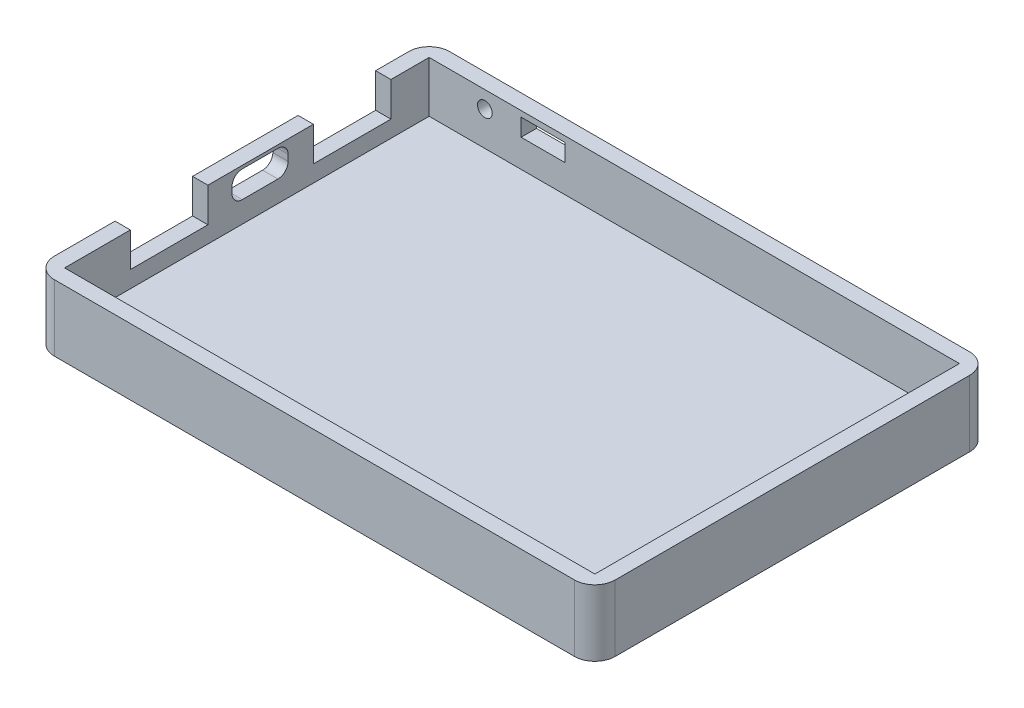
SolidWorks part; units mm, degrees
ref_plane "Front Plane" through (0, 0, 0) normal (0, 0, 1) x (1, 0, 0)
ref_plane "Top Plane" through (0, 0, 0) normal (0, 1, 0) x (1, 0, 0)
ref_plane "Right Plane" through (0, 0, 0) normal (1, 0, 0) x (0, 0, -1)
sketch "Sketch1" plane through (0, 0, 0) normal (0, 1, 0) x (1, 0, 0)
  line L1 (0, 77.5) -> (110, 77.5)
  line L2 (0, 77.5) -> (0, 0)
  line L3 (0, 0) -> (110, 0)
  line L4 (110, 77.5) -> (110, 0)
  line L6 (3, 74.5) -> (3, 3)
  line L7 (3, 3) -> (107, 3)
  line L8 (107, 74.5) -> (107, 3)
  line L9 (3, 74.5) -> (107, 74.5)
  line L10 (0, 73.5) -> (110, 73.5) construction
  line L11 (106, 77.5) -> (106, 0) construction
  point P4 (0, 0)
  dimension "D1" = 3
extrude "Boss-Extrude1" add sketch "Sketch1" along normal blind 10
extrude "Boss-Extrude2" add sketch "Sketch1<2>" against normal blind 3 contours L9 L6 L7 L8 | L4 L1 L2 L3 L6 L9 L8 L7 region at (55, 0, -76.1544) region at (55, 0, -38.75)
sketch "Sketch1<2>" plane through (0, 0, 0) normal (0, 1, 0) x (1, 0, 0) same geometry as "Sketch1"
sketch "Sketch3" plane through (0, 0, 0) normal (-1, 0, 0) x (0, 0, 1)
  line L0 (-66, 10) -> (-66, 4.27) construction
  line L1 (-52.8, 10) -> (-66, 10) construction
  line L2 (-52.8, 10) -> (-52.8, 4.27) construction
  line L3 (-52.8, 4.27) -> (-66, 4.27) construction
  line L4 (-30.1, 10) -> (-30.1, 4.27) construction
  line L5 (-16.9, 4.27) -> (-30.1, 4.27) construction
  line L6 (-16.9, 10) -> (-30.1, 10) construction
  line L7 (-16.9, 10) -> (-16.9, 4.27) construction
  line L8 (-66, 10) -> (-66, 4.27) construction
  line L9 (-52.8, 10) -> (-66, 10) construction
  line L10 (-52.8, 10) -> (-52.8, 4.27) construction
  line L11 (-52.8, 4.27) -> (-66, 4.27) construction
  line L12 (-30.1, 10) -> (-30.1, 4.27) construction
  line L13 (-16.9, 4.27) -> (-30.1, 4.27) construction
  line L14 (-16.9, 10) -> (-30.1, 10) construction
  line L15 (-16.9, 10) -> (-16.9, 4.27) construction
  line L16 (-45.84, 7.38) -> (-45.84, 6.18) construction
  line L17 (-37.84, 8.38) -> (-44.84, 8.38) construction
  line L18 (-36.84, 7.38) -> (-36.84, 6.18) construction
  line L19 (-37.84, 5.18) -> (-44.84, 5.18) construction
  line L20 (-45.84, 7.38) -> (-45.84, 6.18) construction
  line L21 (-37.84, 8.38) -> (-44.84, 8.38) construction
  line L22 (-36.84, 7.38) -> (-36.84, 6.18) construction
  line L23 (-37.84, 5.18) -> (-44.84, 5.18) construction
  line L24 (-15.9, 10) -> (-15.9, 3.27)
  line L25 (-15.9, 3.27) -> (-31.1, 3.27)
  line L26 (-31.1, 10) -> (-31.1, 3.27)
  line L27 (-15.9, 10) -> (-15.9, 3.27) construction
  line L28 (-77.5, 10) -> (0, 10) construction
  line L29 (-31.1, 10) -> (-31.1, 3.27) construction
  line L30 (-51.8, 10) -> (-51.8, 3.27)
  line L31 (-51.8, 3.27) -> (-67, 3.27)
  line L32 (-67, 10) -> (-67, 3.27)
  line L33 (-51.8, 10) -> (-51.8, 3.27) construction
  line L34 (-37.84, 9.38) -> (-44.84, 9.38)
  line L35 (-46.84, 7.38) -> (-46.84, 6.18)
  line L36 (-37.84, 4.18) -> (-44.84, 4.18)
  line L37 (-35.84, 7.38) -> (-35.84, 6.18)
  line L38 (-15.9, 10) -> (-31.1, 10)
  line L39 (-51.8, 10) -> (-67, 10)
  arc A0 (-45.84, 6.18) -> (-44.84, 5.18) centre (-44.84, 6.18) ccw construction
  arc A1 (-44.84, 8.38) -> (-45.84, 7.38) centre (-44.84, 7.38) ccw construction
  arc A2 (-36.84, 7.38) -> (-37.84, 8.38) centre (-37.84, 7.38) ccw construction
  arc A3 (-37.84, 5.18) -> (-36.84, 6.18) centre (-37.84, 6.18) ccw construction
  arc A4 (-45.84, 6.18) -> (-44.84, 5.18) centre (-44.84, 6.18) ccw construction
  arc A5 (-44.84, 8.38) -> (-45.84, 7.38) centre (-44.84, 7.38) ccw construction
  arc A6 (-36.84, 7.38) -> (-37.84, 8.38) centre (-37.84, 7.38) ccw construction
  arc A7 (-37.84, 5.18) -> (-36.84, 6.18) centre (-37.84, 6.18) ccw construction
  arc A8 (-44.84, 9.38) -> (-46.84, 7.38) centre (-44.84, 7.38) ccw
  arc A9 (-46.84, 6.18) -> (-44.84, 4.18) centre (-44.84, 6.18) ccw
  arc A10 (-37.84, 4.18) -> (-35.84, 6.18) centre (-37.84, 6.18) ccw
  arc A11 (-35.84, 7.38) -> (-37.84, 9.38) centre (-37.84, 7.38) ccw
  dimension "D1" = 1
  dimension "D2" = 1
  dimension "D3" = 1
extrude "Cut-Extrude1" cut sketch "Sketch3" against normal up to next
sketch "Sketch4" plane through (0, 0, -77.5) normal (0, 0, -1) x (-1, 0, 0)
  line L0 (-29.14, 8.38) -> (-21.54, 8.38) construction
  line L1 (-29.14, 8.38) -> (-29.14, 5.96) construction
  line L2 (-21.54, 8.38) -> (-21.54, 5.96) construction
  line L3 (-21.54, 5.96) -> (-29.14, 5.96) construction
  line L4 (-29.14, 8.38) -> (-21.54, 8.38) construction
  line L5 (-29.14, 8.38) -> (-29.14, 5.96) construction
  line L6 (-21.54, 8.38) -> (-21.54, 5.96) construction
  line L7 (-21.54, 5.96) -> (-29.14, 5.96) construction
  line L8 (-21.04, 5.46) -> (-29.64, 5.46)
  line L9 (-29.64, 8.88) -> (-29.64, 5.46)
  line L10 (-29.64, 8.88) -> (-21.04, 8.88)
  line L11 (-21.04, 8.88) -> (-21.04, 5.46)
  circle A0 centre (-13.93, 6.69) radius 0.95 construction
  circle A1 centre (-13.93, 6.69) radius 0.95 construction
  circle A2 centre (-13.93, 6.69) radius 1.45
  dimension "D1" = 0.5
extrude "Cut-Extrude2" cut sketch "Sketch4" against normal up to next
fillet "Fillet1" radius 4 4 edges at (110, 3.5, -77.5) (0, 3.5, -77.5) (110, 3.5, 0) (0, 3.5, 0)
